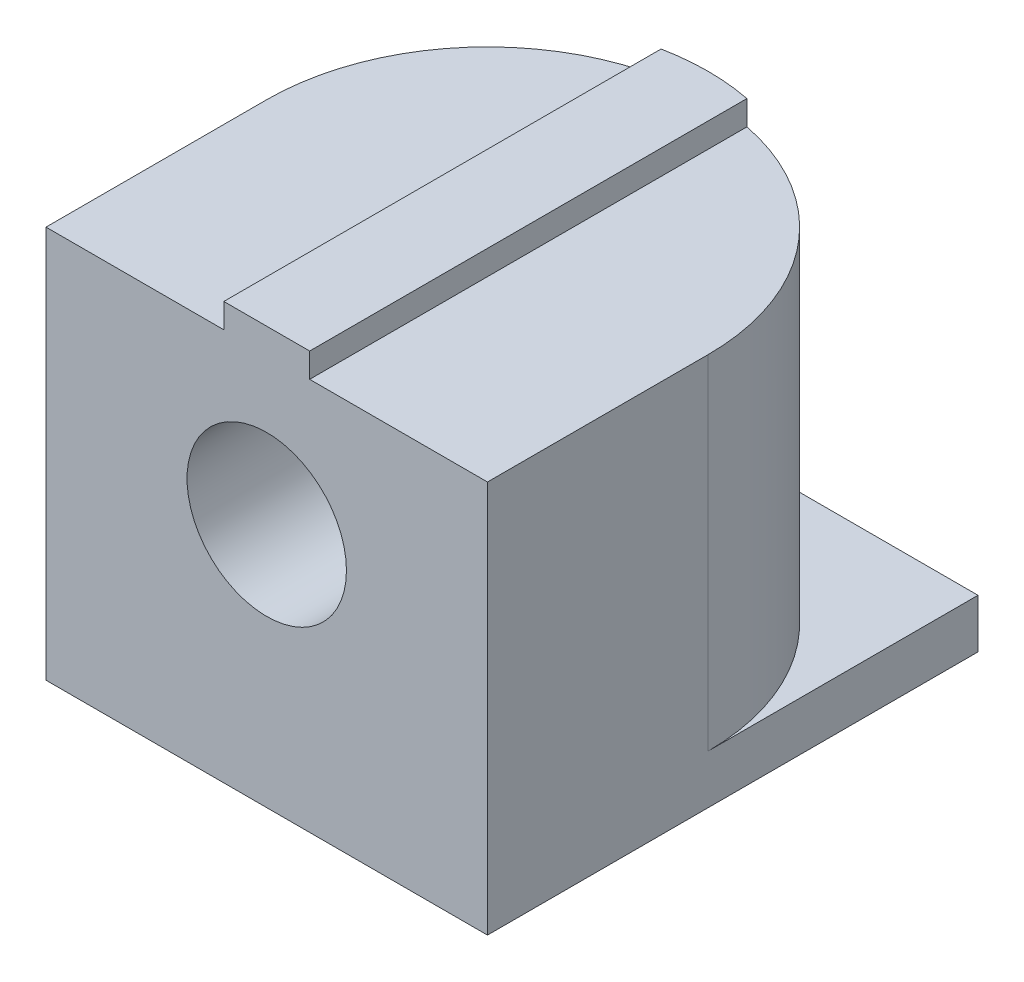
SolidWorks part; units mm, degrees
ref_plane "Front Plane" through (0, 0, 0) normal (0, 0, 1) x (1, 0, 0)
ref_plane "Top Plane" through (0, 0, 0) normal (0, 1, 0) x (1, 0, 0)
ref_plane "Right Plane" through (0, 0, 0) normal (1, 0, 0) x (0, 0, -1)
sketch "Sketch1" plane through (0, 0, 0) normal (0, 1, 0) x (1, 0, 0)
  line L0 (-4.5, 5) -> (4.5, -5) construction
  line L1 (-4.5, -5) -> (4.5, -5)
  line L2 (-4.5, -5) -> (-4.5, 5)
  line L3 (-4.5, 5) -> (4.5, 5)
  line L4 (4.5, -5) -> (4.5, 5)
  dimension "D1" = 9
  dimension "D2" = 10
extrude "Boss-Extrude1" add sketch "Sketch1" along normal blind 1
sketch "Sketch2" plane through (0, 1, 0) normal (0, 1, 0) x (1, 0, 0)
  line L0 (4.5, -5) -> (4.5, 5) construction
  line L1 (-4.5, -5) -> (4.5, -5)
  line L2 (-4.5, -5) -> (-4.5, 4)
  line L3 (-4.5, 4) -> (4.5, 4)
  line L4 (4.5, -5) -> (4.5, 4)
  line L5 (4.5, 5) -> (-4.5, 5) construction
  dimension "D1" = 1
extrude "Boss-Extrude2" add sketch "Sketch2" along normal blind 7
fillet "Fillet1" radius 4.5 2 edges at (-4.5, 4.5, -4) (4.5, 4.5, -4)
sketch "Sketch3" plane through (0, 8, 0) normal (0, 1, 0) x (1, 0, 0)
  line L0 (-4.5, -5) -> (4.5, -5) construction
  line L2 (-0.875, 3.9141) -> (-0.875, -5)
  line L3 (-0.875, -5) -> (0.875, -5)
  line L4 (0.875, 3.9141) -> (0.875, -5)
  line L5 (0, 0) -> (0, -5) construction
  arc A0 (0, 4) -> (-4.5, -0.5) centre (0, -0.5) ccw construction
  arc A1 (4.5, -0.5) -> (0, 4) centre (0, -0.5) ccw construction
  arc A2 (0, 4) -> (-0.875, 3.9141) centre (0, -0.5) ccw
  arc A3 (0.875, 3.9141) -> (0, 4) centre (0, -0.5) ccw
  dimension "D1" = 1.75
extrude "Boss-Extrude3" add sketch "Sketch3" along normal blind 0.5
sketch "Sketch4" plane through (0, 0, 5) normal (0, 0, 1) x (1, 0, 0)
  line L0 (0, 8.5) -> (0, 5) construction
  line L1 (-0.875, 8.5) -> (0.875, 8.5) construction
  line L2 (0.875, 8) -> (4.5, 8) construction
  circle A0 centre (0, 5) radius 1.625
  dimension "D1" = 3.25
  dimension "D2" = 3
extrude "Cut-Extrude1" cut sketch "Sketch4" against normal blind 6
